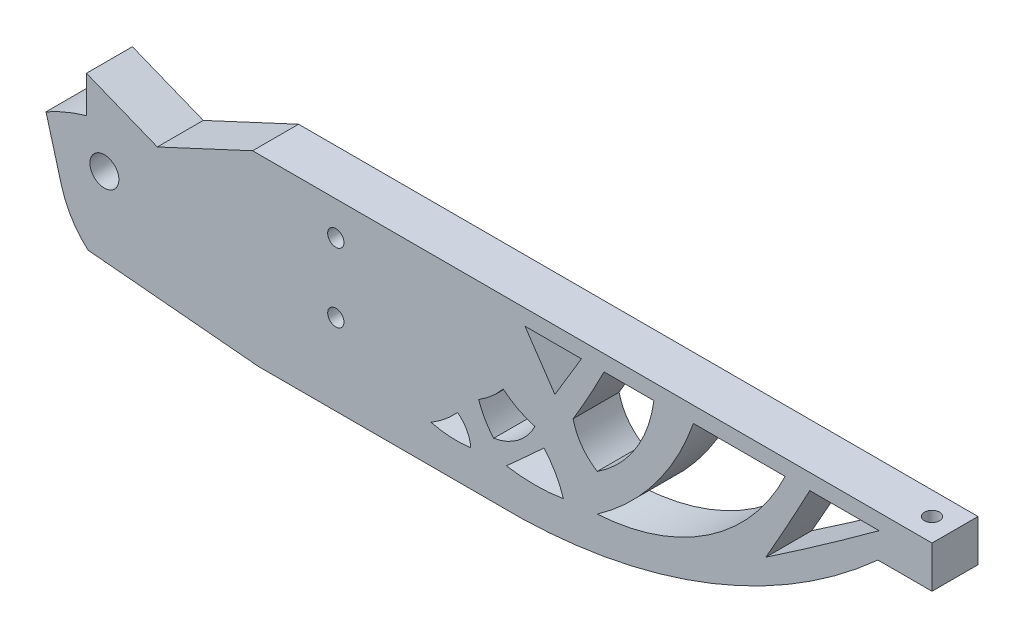
SolidWorks part; units mm, degrees
ref_plane "Front Plane" through (0, 0, 0) normal (0, 0, 1) x (1, 0, 0)
ref_plane "Top Plane" through (0, 0, 0) normal (0, 1, 0) x (1, 0, 0)
ref_plane "Right Plane" through (0, 0, 0) normal (1, 0, 0) x (0, 0, -1)
sketch "Sketch1" plane through (0, 0, 0) normal (0, 0, 1) x (1, 0, 0)
  line L1 (120.65, 25.4) -> (-120.65, 25.4)
  line L2 (120.65, 25.4) -> (120.65, -25.4)
  line L3 (120.65, -25.4) -> (-120.65, -25.4)
  line L4 (-120.65, 25.4) -> (-120.65, -25.4)
  line L5 (120.65, 25.4) -> (-120.65, -25.4) construction
  line L6 (120.65, -25.4) -> (-120.65, 25.4) construction
  point P0 (0, 0)
  dimension "D1" = 241.3
  dimension "D2" = 50.8
extrude "Boss-Extrude1" add sketch "Sketch1" along normal blind 12.7
sketch "Sketch3" plane through (0, 0, 12.7) normal (0, 0, 1) x (1, 0, 0)
  line L0 (0, 0) -> (-120.65, 0) construction
  line L1 (-120.65, 25.4) -> (-120.65, -25.4) construction
  circle A0 centre (-107.95, 0) radius 4
  dimension "D2" = 8
  dimension "D1" = 12.7
extrude "Cut-Extrude1" cut sketch "Sketch3" against normal through all
sketch "Sketch5" plane through (0, 0, 12.7) normal (0, 0, 1) x (1, 0, 0)
  line L0 (-120.65, -25.4) -> (120.65, -25.4) construction
  line L1 (-111.232, -5.4361) -> (-109.6883, -6.1074)
  line L2 (-107.95, 6.35) -> (-67.0151, 25.4)
  line L3 (120.65, 25.4) -> (-120.65, 25.4) construction
  line L4 (-67.0151, 25.4) -> (-120.65, 25.4)
  line L5 (-120.65, 25.4) -> (-120.65, -25.4)
  line L6 (-120.65, -25.4) -> (-65.3282, -25.4)
  line L7 (120.65, 13.8537) -> (120.65, -25.4)
  line L8 (120.65, -25.4) -> (0, -25.4)
  line L9 (120.65, 13.8537) -> (105.7036, 13.8537)
  line L13 (-112.4482, 4.482) -> (-117.3177, 9.3339)
  line L14 (-112.4482, -21.1143) -> (-65.3282, -25.4)
  arc A0 (0, -25.4) -> (105.7036, 13.8537) centre (3.5611, 126.9584) ccw
  arc A1 (-109.9582, -6.0241) -> (-114.0227, -1.8561) centre (-107.95, 0) ccw construction
  arc A2 (-107.95, 6.35) -> (-112.4482, 4.482) centre (-107.95, 0) ccw
  arc A5 (-117.3177, 9.3339) -> (-112.4482, -21.1143) centre (-96.4004, -2.9344) ccw
  point P15 (-116.1445, -2.9908)
  line M3 (-120.65, 25.4) -> (-120.65, -25.4)
  line M4 (-120.65, -25.4) -> (120.65, -25.4)
  line M5 (120.65, -25.4) -> (120.65, 25.4)
  line M6 (120.65, 25.4) -> (-120.65, 25.4)
  dimension "D1" = 152.4
  dimension "D2" = 12.7
  dimension "D3" = 45.1505
  dimension "D4" = 45.9039
extrude "Cut-Extrude2" cut sketch "Sketch5" against normal through all contours A2 L2 L1 M6 M3 M4 | A0 L8 M5 | A5 L5 L14 M4 region at (-102.0317, 17.7416, 12.7) region at (-105.9894, -22.0132, 12.7) region at (91.2141, -11.3337, 12.7)
sketch "Sketch6" plane through (0, 0, 12.7) normal (0, 0, 1) x (1, 0, 0)
  line L0 (-107.95, 0) -> (87.8661, 0) construction
  arc A0 (7.1222, -25.4) -> (105.7036, 13.8537) centre (3.5611, 126.9584) ccw construction
  circle A1 centre (19.05, 0) radius 3.1347
  dimension "D1" = 127
sketch "Sketch7" plane through (0, 0, 0) normal (0, 0, -1) x (-1, 0, 0)
  line L0 (44.0204, -2.9977) -> (44.0204, 16.0523) construction
  point P3 (44.0204, -2.9977)
  point P4 (44.0204, 16.0523)
  dimension "D1" = 19.05
sketch "Sketch8" plane through (0, 0, 0) normal (0, 0, -1) x (-1, 0, 0)
  point P0 (44.0204, 16.0523)
  point P3 (44.0204, -2.9977)
hole_wizard "#8 Clearance Hole1" positions "Sketch8" profile "Sketch9" hole size "#8" standard "ANSI Inch" end condition through all
sketch "Sketch9" plane through (-44.0204, 16.0523, 0) normal (1, 0, 0) x (0, 1, 0)
  line L0 (0, 0) -> (0, 12.7)
  line L1 (0, 12.7) -> (2.2479, 12.7)
  line L2 (2.2479, 12.7) -> (2.2479, 0)
  line L5 (2.2479, 0) -> (0, 0)
  line L11 (0, -6.35) -> (0, 107.95) construction
  dimension "Thru Hole Dia." = 4.4958
  dimension "Thru Hole Depth" = 12.7
ref_plane "Plane1" through (-114.3, 0, 0) normal (-1, 0, 0) x (0, 0, 1)
sketch "Sketch10" plane through (-114.3, 0, 0) normal (-1, 0, 0) x (0, 0, 1)
  line L0 (0, 0) -> (12.7, 0) construction
  line L1 (12.7, -3.1347) -> (12.7, 3.1347) construction
  circle A0 centre (6.0894, 0) radius 1.905
  dimension "D1" = 3.81
sketch "Sketch11" plane through (0, 0, 12.7) normal (0, 0, 1) x (1, 0, 0)
  line L0 (-93.8249, 12.9234) -> (-109.4459, 12.9234) construction
  line L1 (-107.95, 6.35) -> (-67.0151, 25.4) construction
  line L2 (-109.4459, 12.9234) -> (-109.4459, 11.5568) construction
  line L3 (-93.8249, 12.9234) -> (-109.4459, 5.6538)
  line L10 (-119.777, -9.3826) -> (-115.4906, -1.5141)
  line L11 (-115.4906, -1.5141) -> (-109.4459, 5.6538)
  line L12 (-124.0726, 6.1903) -> (-119.777, -9.3826)
  arc A0 (-117.3177, 9.3339) -> (-112.4482, -21.1143) centre (-96.4004, -2.9344) ccw construction
  circle A1 centre (-107.95, 0) radius 4 construction
  arc A4 (-124.0726, 6.1903) -> (-93.8249, 12.9234) centre (-97.649, -41.2057) cw
  dimension "D2" = 5.6538
extrude "Boss-Extrude2" add sketch "Sketch11" against normal up to surface (12.7 mm away) up to face at (-46.2683, 16.0523, 0)
sketch "Sketch18" plane through (0, 25.4, 0) normal (0, 1, 0) x (1, 0, 0)
  circle A0 centre (114.3, -6.35) radius 2.0828
extrude "Cut-Extrude9" cut sketch "Sketch18" against normal through all contours A0
sketch "Sketch19" plane through (0, 0, 12.7) normal (0, 0, 1) x (1, 0, 0)
  line L3 (86.8867, 21.0579) -> (106.0483, 21.0579)
  line L4 (54.7502, 21.0579) -> (80.0838, 21.0579)
  line L5 (43.8283, 21.0579) -> (30.0654, 21.0579)
  line L6 (21.5195, 21.0579) -> (8.2267, 21.0579)
  line L7 (8.2267, 21.0579) -> (16.4852, 8.8568)
  line L8 (16.4852, 8.8568) -> (23.8201, 21.0579)
  line L9 (23.8201, 21.0579) -> (21.5195, 21.0579)
  arc A0 (106.0483, 21.0579) -> (74.7548, -0.9382) centre (-476.4178, 816.4626) cw
  arc A1 (86.8867, 21.0579) -> (74.7548, -0.9382) centre (-617.5859, 395.2635) cw
  arc A2 (80.0838, 21.0579) -> (28.1833, -13.9058) centre (24.5582, 47.4779) cw
  arc A3 (28.1833, -13.9058) -> (54.7502, 21.0579) centre (-12.7332, 44.7595) ccw
  arc A4 (30.0654, 21.0579) -> (21.5195, 5.5624) centre (-173.1779, 123.0437) cw
  arc A5 (43.8283, 21.0579) -> (28.1833, -3.6987) centre (9.3178, 25.5453) cw
  arc A6 (28.1833, -3.6987) -> (21.5195, 5.5624) centre (35.8652, 8.8568) cw
  arc A7 (3.09, -14.9046) -> (13.4624, -5.4583) centre (-508.9074, 557.7064) ccw
  arc A8 (13.4624, -5.4583) -> (18.8338, -14.9046) centre (-5.5007, -22.4915) cw
  arc A9 (18.8338, -14.9046) -> (3.09, -14.9046) centre (10.9619, 32.5583) cw
  arc A10 (2.2235, 3.0165) -> (-4.5776, -2.8864) centre (-19.0872, 20.7005) cw
  arc A11 (2.2235, 3.0165) -> (10.9619, -1.539) centre (16.8059, 20.3296) ccw
  arc A12 (10.9619, -1.539) -> (-0.4071, -10.0726) centre (-3.0644, 5.3078) cw
  arc A13 (-4.5776, -2.8864) -> (-0.4071, -10.0726) centre (15.1613, 3.7659) ccw
  arc A14 (-10.4164, -8.9177) -> (-6.7592, -15.5263) centre (-15.593, -16.0987) cw
  arc A15 (-6.7592, -15.5263) -> (-17.7308, -14.9046) centre (-10.6309, 13.2663) cw
  arc A16 (-17.7308, -14.9046) -> (-10.4164, -8.9177) centre (-33.6495, 12.0056) ccw
extrude "Cut-Extrude10" cut sketch "Sketch19" against normal through all
pattern_linear "LPattern1" [suppressed] count 5 spacing 6.35 of bodies 117
sketch "Sketch20" plane through (0, 0, 12.7) normal (0, 0, 1) x (1, 0, 0)
  line L0 (-112.9039, 9.7778) -> (-112.9039, 20.995)
  line L2 (-112.9039, 20.995) -> (-92.9368, 13.0011)
  line L3 (-92.9368, 13.0011) -> (-112.9039, 9.7778)
  point P5 (-112.8075, 11.2629)
  point P6 (-112.8075, 9.7939)
  point P7 (-113.1344, 24.178)
  point P8 (-112.9039, 20.995)
  point P9 (-92.9368, 13.0011)
extrude "Boss-Extrude3" add sketch "Sketch20" against normal up to vertex (12.7 mm away) up to point (-124.0726, 6.1903, 0)
